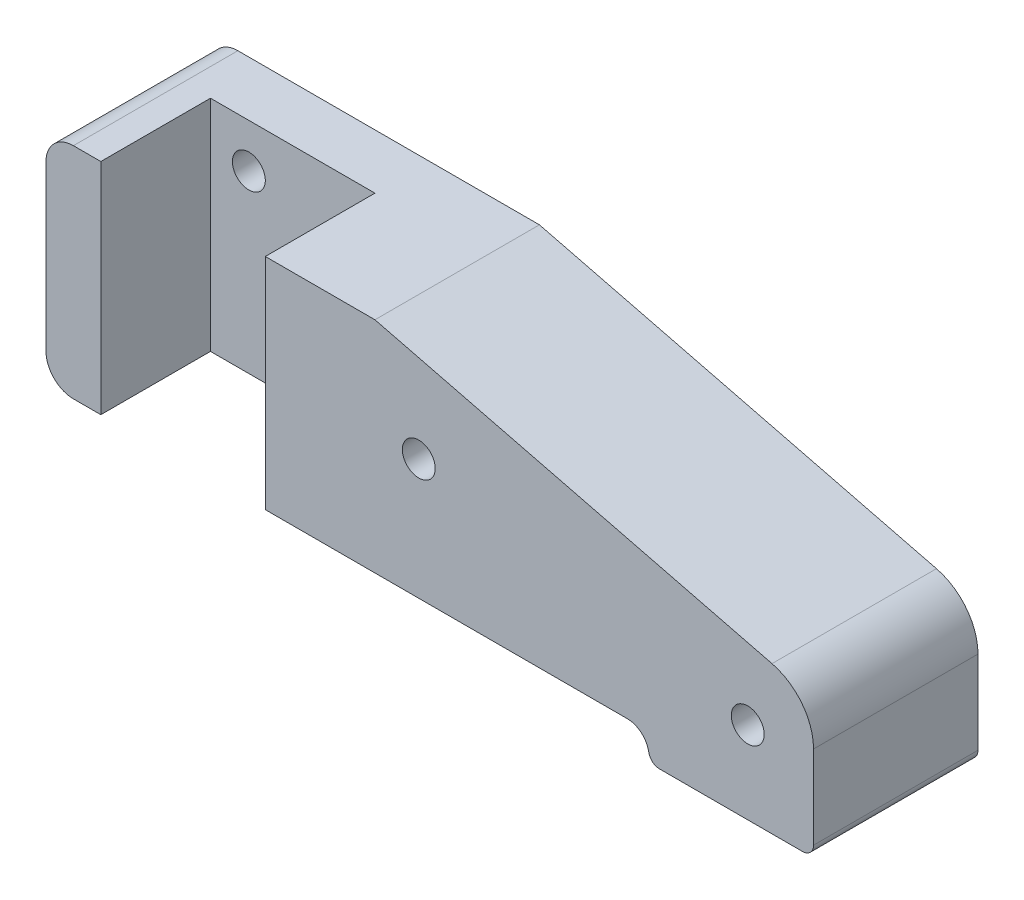
SolidWorks part; units mm, degrees
ref_plane "Front" through (0, 0, 0) normal (0, 0, 1) x (1, 0, 0)
ref_plane "Top" through (0, 0, 0) normal (0, 1, 0) x (1, 0, 0)
ref_plane "Right" through (0, 0, 0) normal (1, 0, 0) x (0, 0, -1)
sketch "Esquisse1" plane through (0, 0, 0) normal (0, 0, 1) x (1, 0, 0)
  line L1 (0, 0) -> (140, 0)
  line L2 (0, 0) -> (0, 40)
  line L3 (0, 40) -> (140, 40)
  line L4 (140, 0) -> (140, 40)
  dimension "D1" = 140
  dimension "D2" = 40
extrude "Boss.-Extru.1" add sketch "Esquisse1" along normal blind 30
sketch "Esquisse2" plane through (0, 0, 30) normal (0, 0, 1) x (1, 0, 0)
  line L0 (0, 0) -> (140, 0) construction
  line L1 (10, 0) -> (40, 0)
  line L2 (10, 0) -> (10, 40)
  line L3 (10, 40) -> (40, 40)
  line L4 (40, 0) -> (40, 40)
  line L5 (140, 40) -> (0, 40) construction
  line L6 (0, 40) -> (0, 0) construction
  dimension "D1" = 10
  dimension "D2" = 30
extrude "Enlèv. mat.-Extru.1" cut sketch "Esquisse2" against normal blind 20
sketch "Esquisse3" plane through (0, 0, 30) normal (0, 0, 1) x (1, 0, 0)
  line L0 (140, 20) -> (60, 40)
  line L1 (140, 0) -> (140, 40) construction
  line L2 (140, 40) -> (40, 40) construction
  line L3 (60, 40) -> (140, 40)
  line L4 (140, 40) -> (140, 20)
  dimension "D1" = 20
  dimension "D2" = 80
extrude "Enlèv. mat.-Extru.2" cut sketch "Esquisse3" against normal through all both and the other way through all
sketch "Esquisse5" plane through (0, 0, 30) normal (0, 0, 1) x (1, 0, 0)
  line L0 (25, 0) -> (25, 40) construction
  line L1 (10, 0) -> (40, 0) construction
  line L2 (40, 40) -> (10, 40) construction
  line L3 (25, 20) -> (10, 20) construction
  line L4 (10, 40) -> (10, 0) construction
  line L5 (140, 10) -> (128, 10) construction
  line L6 (140, 0) -> (140, 20) construction
  circle A0 centre (17, 32) radius 3
  circle A1 centre (33, 8) radius 3
  circle A2 centre (68, 22) radius 3
  circle A3 centre (128, 10) radius 3
  dimension "D1" = 6
  dimension "D3" = 16
  dimension "D4" = 12
  dimension "D5" = 16
  dimension "D7" = 12
  dimension "D8" = 60
  dimension "D2" = 12
  dimension "D6" = 12
extrude "Enlèv. mat.-Extru.6" cut sketch "Esquisse5" against normal through all both and the other way through all
fillet "Congé1" radius 10 1 edges at (140, 20, 15)
sketch "Esquisse6" plane through (0, 0, 30) normal (0, 0, 1) x (1, 0, 0)
  line L1 (140, 0) -> (110, 0)
  line L2 (140, 0) -> (140, -5)
  line L3 (140, -5) -> (110, -5)
  line L4 (110, 0) -> (110, -5)
  dimension "D1" = 5
  dimension "D2" = 30
extrude "Boss.-Extru.2" add sketch "Esquisse6" against normal up to vertex (30 mm away) up to point (140, 0, 0)
sketch "Esquisse4" plane through (0, 0, 0) normal (0, 0, -1) x (-1, 0, 0)
  line L5 (-60, 40) -> (-132.4254, 21.8937)
  line L6 (-140, 12.1922) -> (-140, -5)
  line L7 (-110, 0) -> (0, 0)
  line L8 (0, 0) -> (0, 40)
  line L9 (0, 40) -> (-60, 40)
  line L10 (-60, 40) -> (-132.4254, 21.8937)
  line L11 (-140, 12.1922) -> (-140, -5)
  line L12 (-110, 0) -> (0, 0)
  line L13 (0, 0) -> (0, 40)
  line L14 (0, 40) -> (-60, 40)
  line L17 (-140, -5) -> (-110, -5)
  line L18 (-140, -5) -> (-110, -5)
  line L19 (-110, -5) -> (-110, 0)
  line L20 (-110, -5) -> (-110, 0)
  arc A1 (-132.4254, 21.8937) -> (-140, 12.1922) centre (-130, 12.1922) ccw
  arc A2 (-132.4254, 21.8937) -> (-140, 12.1922) centre (-130, 12.1922) ccw
  dimension "D1" = 0
extrude "Enlèv. mat.-Extru.5" [suppressed] cut sketch "Esquisse4" against normal through all from offset 10 offset against normal yes
fillet "Congé2" radius 4 1 edges at (110, 0, 15)
fillet "Congé3" radius 2 2 edges at (140, -5, 15) (110, -5, 15)
fillet "Congé4" radius 5 2 edges at (0, 40, 15) (0, 0, 15)
